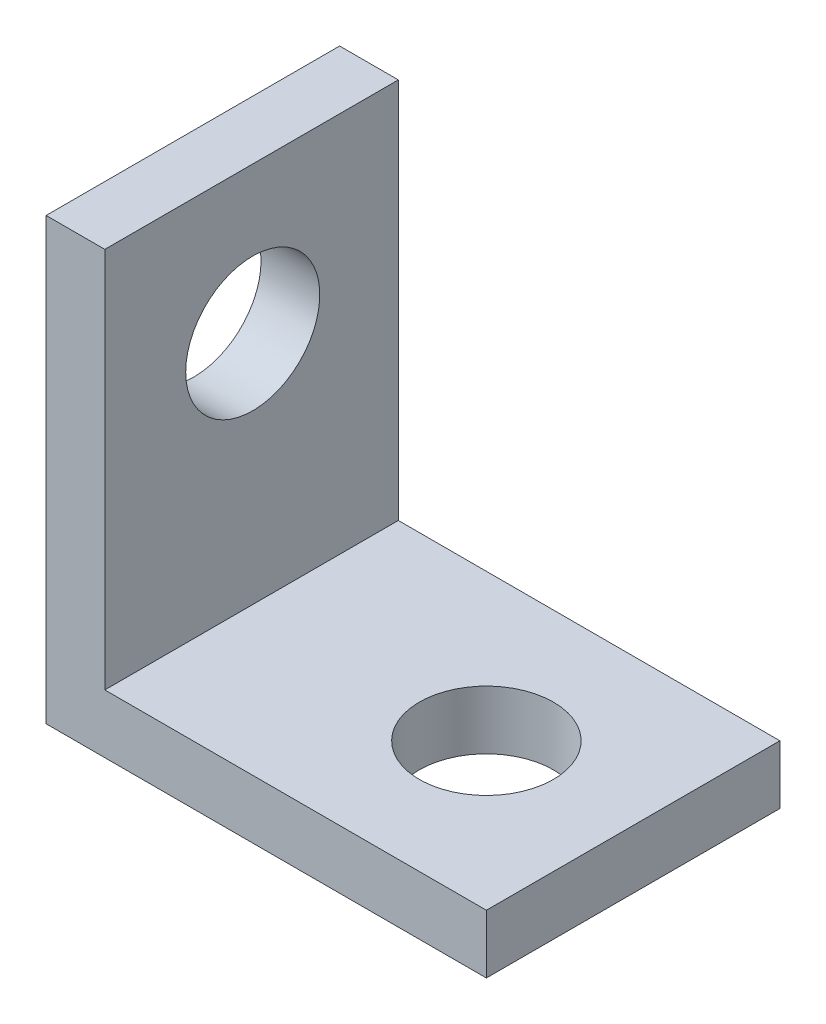
SolidWorks part; units mm, degrees
material "6061 Alloy"
ref_plane "Front Plane" through (0, 0, 0) normal (0, 0, 1) x (1, 0, 0)
ref_plane "Top Plane" through (0, 0, 0) normal (0, 1, 0) x (1, 0, 0)
ref_plane "Right Plane" through (0, 0, 0) normal (1, 0, 0) x (0, 0, -1)
sketch "Sketch1" plane through (0, 0, 0) normal (0, 0, 1) x (1, 0, 0)
  line L0 (0, 0) -> (0, 19.05)
  line L1 (0, 0) -> (19.05, 0)
  line L2 (2.54, 2.54) -> (19.05, 2.54)
  line L3 (2.54, 2.54) -> (2.54, 19.05)
  line L4 (0, 19.05) -> (2.54, 19.05)
  line L5 (19.05, 0) -> (19.05, 2.54)
  dimension "D1" = 19.05
  dimension "D2" = 2.54
  dimension ".5in" = 19.05
extrude "Boss-Extrude1" add sketch "Sketch1" along normal blind 12.7
sketch "Sketch2" plane through (0, 0, 0) normal (1, 0, 0) x (0, 0, -1)
  line L0 (-6.2999, 19.05) -> (-6.2999, 0) construction
  line L1 (-12.7, 19.05) -> (0, 19.05) construction
  line L2 (-12.7, 0) -> (0, 0) construction
  circle A0 centre (-6.2999, 12.7) radius 2.9
  dimension "D1" = 5.8
  dimension "D2" = 12.7
extrude "Cut-Extrude1" cut sketch "Sketch2" along normal blind 12.7
sketch "Sketch3" plane through (0, 0, 0) normal (0, 1, 0) x (1, 0, 0)
  line L0 (19.05, -6.35) -> (0, -6.35) construction
  line L1 (19.05, -12.7) -> (19.05, 0) construction
  line L2 (0, -12.7) -> (0, 0) construction
  circle A0 centre (12.7, -6.35) radius 2.9
  dimension "D1" = 5.8
  dimension "D2" = 12.7
extrude "Cut-Extrude3" cut sketch "Sketch3" along normal blind 12.7
